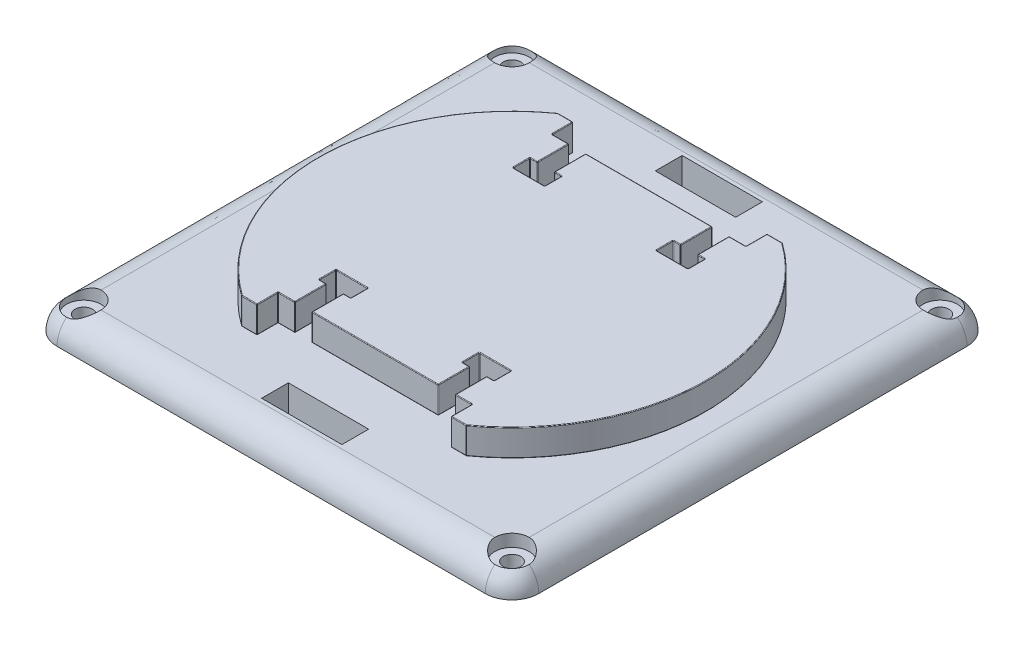
SolidWorks part; units mm, degrees
ref_plane "Front Plane" through (0, 0, 0) normal (0, 0, 1) x (1, 0, 0)
ref_plane "Top Plane" through (0, 0, 0) normal (0, 1, 0) x (1, 0, 0)
ref_plane "Right Plane" through (0, 0, 0) normal (1, 0, 0) x (0, 0, -1)
sketch "Sketch1" plane through (0, 0, 0) normal (0, 1, 0) x (1, 0, 0)
  line L0 (-26.6411, 37.5) -> (-23, 37.5)
  line L1 (23, 37.5) -> (26.6411, 37.5)
  line L3 (-23, 37.5) -> (-23, 32.5)
  line L4 (-23, 32.5) -> (23, 32.5)
  line L5 (23, 37.5) -> (23, 32.5)
  line L6 (0, 0) -> (-46, 0) construction
  line L7 (23, -37.5) -> (26.6411, -37.5)
  line L8 (23, -37.5) -> (23, -32.5)
  line L9 (-23, -32.5) -> (23, -32.5)
  line L10 (-23, -37.5) -> (-23, -32.5)
  line L11 (-26.6411, -37.5) -> (-23, -37.5)
  arc A0 (-26.6411, 37.5) -> (-26.6411, -37.5) centre (0, 0) ccw
  arc A1 (26.6411, -37.5) -> (26.6411, 37.5) centre (0, 0) ccw
  point P10 (0, 32.5)
  dimension "D1" = 92
  dimension "D2" = 37.5
  dimension "D3" = 46
  dimension "D4" = 5
extrude "Boss-Extrude1" add sketch "Sketch1" along normal blind 6.35
sketch "Sketch2" plane through (0, 6.35, 0) normal (0, 1, 0) x (1, 0, 0)
  line L0 (23, 32.5) -> (-23, 32.5) construction
  line L1 (-19, 25) -> (-15, 25)
  line L2 (-19, 25) -> (-19, 32.5)
  line L3 (-19, 32.5) -> (-15, 32.5)
  line L4 (-15, 25) -> (-15, 32.5)
  line L5 (-19, 25) -> (-15, 32.5) construction
  line L6 (-19, 32.5) -> (-15, 25) construction
  line L7 (-23, 32.5) -> (-23, 37.5) construction
  line L8 (-13.25, 21) -> (-20.75, 21)
  line L9 (-13.25, 21) -> (-13.25, 25)
  line L10 (-13.25, 25) -> (-20.75, 25)
  line L11 (-20.75, 21) -> (-20.75, 25)
  line L12 (-13.25, 21) -> (-20.75, 25) construction
  line L13 (-13.25, 25) -> (-20.75, 21) construction
  line L14 (0, 0) -> (-46, 0) construction
  line L15 (0, 0) -> (0, 32.5) construction
  line L16 (13.25, 25) -> (20.75, 21) construction
  line L17 (13.25, 21) -> (20.75, 25) construction
  line L18 (19, 32.5) -> (15, 25) construction
  line L19 (19, 25) -> (15, 32.5) construction
  line L20 (20.75, 21) -> (20.75, 25)
  line L21 (13.25, 25) -> (20.75, 25)
  line L22 (13.25, 21) -> (13.25, 25)
  line L23 (13.25, 21) -> (20.75, 21)
  line L24 (15, 25) -> (15, 32.5)
  line L25 (19, 32.5) -> (15, 32.5)
  line L26 (19, 25) -> (19, 32.5)
  line L27 (19, 25) -> (15, 25)
  line L28 (19, -25) -> (15, -32.5) construction
  line L29 (19, -32.5) -> (15, -25) construction
  line L30 (13.25, -21) -> (20.75, -25) construction
  line L31 (13.25, -25) -> (20.75, -21) construction
  line L32 (-13.25, -25) -> (-20.75, -21) construction
  line L33 (-13.25, -21) -> (-20.75, -25) construction
  line L34 (-19, -32.5) -> (-15, -25) construction
  line L35 (-19, -25) -> (-15, -32.5) construction
  line L36 (19, -25) -> (15, -25)
  line L37 (19, -25) -> (19, -32.5)
  line L38 (19, -32.5) -> (15, -32.5)
  line L39 (15, -25) -> (15, -32.5)
  line L40 (13.25, -21) -> (20.75, -21)
  line L41 (13.25, -21) -> (13.25, -25)
  line L42 (13.25, -25) -> (20.75, -25)
  line L43 (20.75, -21) -> (20.75, -25)
  line L44 (-20.75, -21) -> (-20.75, -25)
  line L45 (-13.25, -25) -> (-20.75, -25)
  line L46 (-13.25, -21) -> (-13.25, -25)
  line L47 (-13.25, -21) -> (-20.75, -21)
  line L48 (-15, -25) -> (-15, -32.5)
  line L49 (-19, -32.5) -> (-15, -32.5)
  line L50 (-19, -25) -> (-19, -32.5)
  line L51 (-19, -25) -> (-15, -25)
  arc A0 (-26.6411, 37.5) -> (-26.6411, -37.5) centre (0, 0) ccw construction
  point P0 (-17, 28.75)
  point P7 (-17, 23)
  point P29 (17, 23)
  point P30 (17, 28.75)
  point P47 (17, -28.75)
  point P48 (17, -23)
  point P49 (-17, -23)
  point P50 (-17, -28.75)
  dimension "D1" = 4
  dimension "D2" = 4
  dimension "D3" = 7.5
  dimension "D4" = 4
  dimension "D5" = 7.5
extrude "Cut-Extrude1" cut sketch "Sketch2" against normal through all contours L4 L3 L2 L1 | L9 L10 L11 L8 | L26 L25 L24 L27 | L20 L21 L22 L23 | L43 L42 L41 L40 | L37 L38 L39 L36 | L48 L49 L50 L51 | L46 L45 L44 L47
fillet "Fillet1" radius 0.15 132 edges at (-19, 3.175, -32.5) (-19, 6.35, -28.75) (-21, 6.35, -32.5) (-19, 0, -28.75) (-19, 3.175, -25) (-23, 3.175, -32.5) (-21, 0, -32.5) (-19.875, 6.35, -25) (-23, 6.35, -35) (-19.875, 0, -25) (-20.75, 3.175, -25) (-23, 3.175, -37.5) (-23, 0, -35) (-20.75, 6.35, -23) (-24.8206, 6.35, -37.5) (-20.75, 0, -23) (-20.75, 3.175, -21) (-26.6411, 3.175, -37.5) (-24.8206, 0, -37.5) (-17, 6.35, -21) (-46, 6.35, 0) (-17, 0, -21) (-13.25, 3.175, -21) (-26.6411, 3.175, 37.5) (-46, 0, 0) (-13.25, 6.35, -23) (-24.8206, 6.35, 37.5) (-13.25, 0, -23) (-13.25, 3.175, -25) (-23, 3.175, 37.5) (-24.8206, 0, 37.5) (-14.125, 6.35, -25) (-23, 6.35, 35) (-14.125, 0, -25) (-15, 3.175, -25) (-23, 3.175, 32.5) (-23, 0, 35) (-15, 6.35, -28.75) (-21, 6.35, 32.5) (-15, 0, -28.75) (-15, 3.175, -32.5) (-21, 0, 32.5) (-19, 3.175, 32.5) (0, 6.35, -32.5) (-19, 6.35, 28.75) (0, 0, -32.5) (15, 3.175, -32.5) (-19, 0, 28.75) (-19, 3.175, 25) (15, 6.35, -28.75) (-19.875, 6.35, 25) (15, 0, -28.75) (15, 3.175, -25) (-20.75, 3.175, 25) (-19.875, 0, 25) (14.125, 6.35, -25) (-20.75, 6.35, 23) (14.125, 0, -25) (13.25, 3.175, -25) (-20.75, 0, 23) (-20.75, 3.175, 21) (13.25, 6.35, -23) (-17, 6.35, 21) (13.25, 0, -23) (13.25, 3.175, -21) (-17, 0, 21) (-13.25, 3.175, 21) (17, 6.35, -21) (-13.25, 6.35, 23) (17, 0, -21) (20.75, 3.175, -21) (-13.25, 0, 23) (-13.25, 3.175, 25) (20.75, 6.35, -23) (-14.125, 6.35, 25) (20.75, 0, -23) (20.75, 3.175, -25) (-14.125, 0, 25) (-15, 3.175, 25) (19.875, 6.35, -25) (-15, 6.35, 28.75) (19.875, 0, -25) (19, 3.175, -25) (-15, 3.175, 32.5) (-15, 0, 28.75) (19, 6.35, -28.75) (0, 6.35, 32.5) (19, 0, -28.75) (19, 3.175, -32.5) (0, 0, 32.5) (15, 3.175, 32.5) (21, 6.35, -32.5) (15, 6.35, 28.75) (21, 0, -32.5) (23, 3.175, -32.5) (15, 0, 28.75) (15, 3.175, 25) (23, 6.35, -35) (14.125, 6.35, 25) (23, 0, -35) (23, 3.175, -37.5) (14.125, 0, 25) (13.25, 3.175, 25) (24.8206, 6.35, -37.5) (13.25, 6.35, 23) (24.8206, 0, -37.5) (26.6411, 3.175, -37.5) (13.25, 0, 23) (13.25, 3.175, 21) (46, 6.35, 0) (17, 6.35, 21) (46, 0, 0) (26.6411, 3.175, 37.5) (20.75, 3.175, 21) (17, 0, 21) (24.8206, 6.35, 37.5) (20.75, 6.35, 23) (23, 3.175, 37.5) (24.8206, 0, 37.5) (20.75, 3.175, 25) (20.75, 0, 23) (23, 6.35, 35) (19.875, 6.35, 25) (23, 0, 35) (23, 3.175, 32.5) (19, 3.175, 25) (19.875, 0, 25) (21, 6.35, 32.5) (19, 6.35, 28.75) (21, 0, 32.5) (19, 0, 28.75) (19, 3.175, 32.5)
sketch "Sketch3" plane through (0, 0, 0) normal (0, -1, 0) x (1, 0, 0)
  line L0 (0, 0) -> (0, -57.15) construction
  line L1 (-57.15, 57.15) -> (57.15, 57.15)
  line L2 (-57.15, 57.15) -> (-57.15, -57.15)
  line L3 (-57.15, -57.15) -> (57.15, -57.15)
  line L4 (57.15, 57.15) -> (57.15, -57.15)
  line L5 (-57.15, 57.15) -> (57.15, -57.15) construction
  line L6 (-57.15, -57.15) -> (57.15, 57.15) construction
  line L8 (0, 0) -> (-57.15, 0) construction
  line L9 (0, 0) -> (0, -57.15) construction
  line L10 (0, 0) -> (-57.15, 0) construction
  point P0 (0, 0)
  point P7 (57.15, -57.15)
  point P10 (-57.15, -57.15)
  point P11 (-57.15, 57.15)
  point P12 (57.15, 57.15)
  point P13 (-57.15, 0)
  point P14 (57.15, -57.15)
  point P16 (-57.15, -57.15)
  point P17 (-57.15, 57.15)
  dimension "D1" = 114.3
  dimension "D2" = 114.3
extrude "Boss-Extrude2" add sketch "Sketch3" along normal blind 6.35
fillet "Fillet4" radius 6.35 1 edges at (57.15, 0, 0)
fillet "Fillet5" radius 6.35 2 edges
fillet "Fillet6" radius 6.35 2 edges
fillet "Fillet7" radius 6.35 3 edges
sketch "Sketch4" plane through (0, 0, 0) normal (0, -1, 0) x (-1, 0, 0)
  line L0 (0, 0) -> (0, 50.8) construction
  line L1 (-50.8, 50.8) -> (50.8, 50.8) construction
  line L2 (0, 0) -> (-50.8, 0) construction
  line L3 (-50.8, -50.8) -> (-50.8, 50.8) construction
  circle A1 centre (-50.8, 50.8) radius 4.0894
  circle A2 centre (-50.8, 50.8) radius 2.0828
  circle A3 centre (50.8, 50.8) radius 2.0828
  circle A4 centre (50.8, 50.8) radius 4.0894
  circle A5 centre (-50.8, -50.8) radius 2.0828
  circle A6 centre (-50.8, -50.8) radius 4.0894
  circle A7 centre (50.8, -50.8) radius 2.0828
  circle A8 centre (50.8, -50.8) radius 4.0894
extrude "Cut-Extrude3" cut sketch "Sketch4" along normal blind 2.921 contours A2 | A1 | A4 | A3 | A5 | A6 | A7 | A8
sketch "Sketch5" plane through (0, 0, 0) normal (0, 1, 0) x (1, 0, 0)
  line L0 (0, 0) -> (0, 50.8) construction
  line L1 (46.7106, 50.8) -> (-46.7106, 50.8) construction
  line L2 (0, 0) -> (50.8, 0) construction
  line L3 (50.8, -46.7106) -> (50.8, 46.7106) construction
  circle A0 centre (50.8, 50.8) radius 2.0828
  circle A1 centre (-50.8, 50.8) radius 2.0828
  circle A2 centre (50.8, -50.8) radius 2.0828
  circle A3 centre (-50.8, -50.8) radius 2.0828
extrude "Cut-Extrude4" cut sketch "Sketch5" against normal through all
sketch "Sketch6" plane through (0, 0, 0) normal (0, 1, 0) x (1, 0, 0)
  line L0 (0, 50.8) -> (0, -50.8) construction
  line L1 (46.7106, 50.8) -> (-46.7106, 50.8) construction
  line L2 (-46.7106, -50.8) -> (46.7106, -50.8) construction
  line L3 (-50.8, 0) -> (50.8, 0) construction
  line L4 (-50.8, 46.7106) -> (-50.8, -46.7106) construction
  line L5 (50.8, -46.7106) -> (50.8, 46.7106) construction
  line L6 (-50.8, -46.7106) -> (50.8, -46.7106) construction
  line L7 (-9.525, 49.8856) -> (-9.525, 43.5356)
  line L8 (-9.525, -49.8856) -> (9.525, -49.8856)
  line L9 (-9.525, -49.8856) -> (-9.525, -43.5356)
  line L10 (-9.525, -43.5356) -> (9.525, -43.5356)
  line L11 (9.525, -49.8856) -> (9.525, -43.5356)
  line L12 (-9.525, -49.8856) -> (9.525, -43.5356) construction
  line L13 (-9.525, -43.5356) -> (9.525, -49.8856) construction
  line L14 (-9.525, 49.8856) -> (9.525, 49.8856)
  line L15 (9.525, 49.8856) -> (9.525, 43.5356)
  line L16 (-9.525, 43.5356) -> (9.525, 43.5356)
  point P16 (0, -46.7106)
  dimension "D1" = 6.35
  dimension "D2" = 19.05
extrude "Cut-Extrude5" cut sketch "Sketch6" against normal through all
